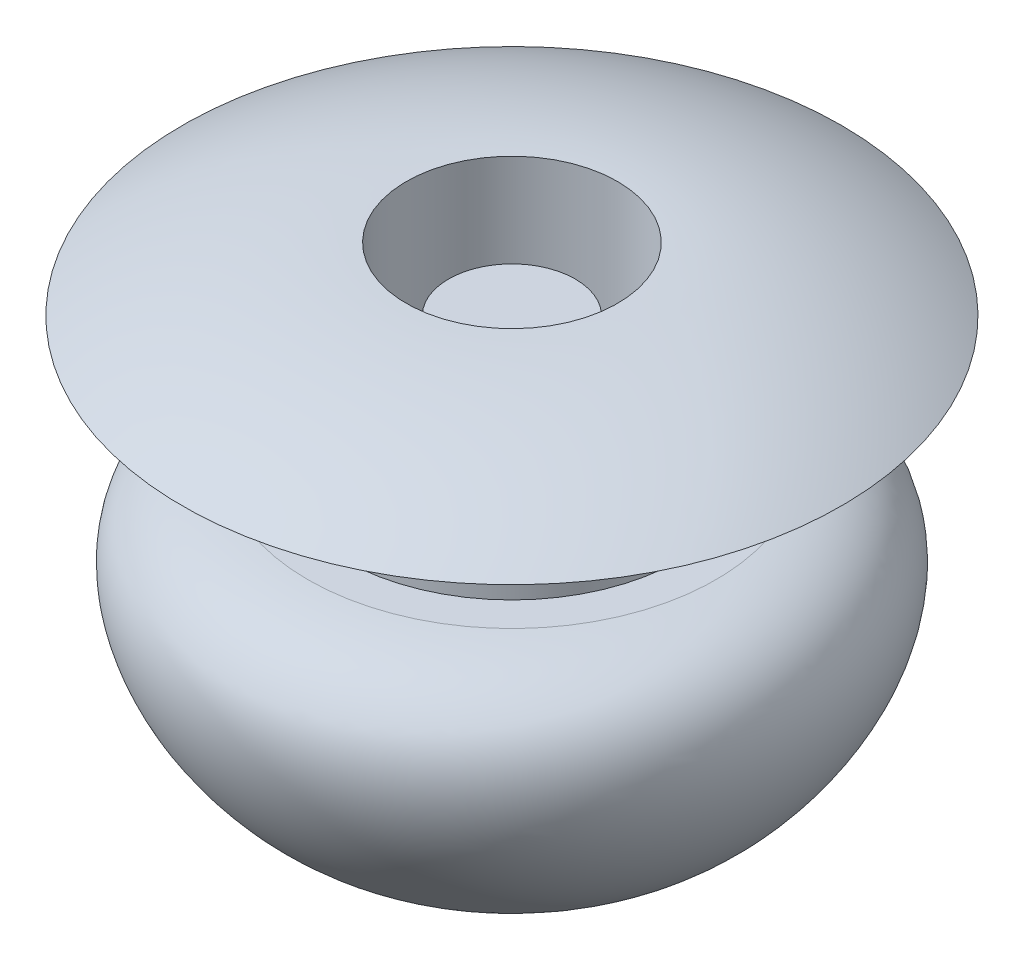
SolidWorks part; units mm, degrees
material "AISI 316 Stal nierdzewna odprężona (SS)"
ref_plane "Płaszczyzna przednia" through (0, 0, 0) normal (0, 0, 1) x (1, 0, 0)
ref_plane "Płaszczyzna górna" through (0, 0, 0) normal (0, 1, 0) x (1, 0, 0)
ref_plane "Płaszczyzna prawa" through (0, 0, 0) normal (1, 0, 0) x (0, 0, -1)
sketch "Szkic1" plane through (0, 0, 0) normal (1, 0, 0) x (0, 0, -1)
  line L1 (0, 0) -> (-0.75, 0)
  line L2 (-0.75, 0) -> (-0.75, -1.7007)
  line L3 (-0.75, -1.7007) -> (-1.25, -1.7007)
  line L4 (-1.25, -1.7007) -> (-1.25, 0.75)
  line L5 (-3.9, 0) -> (-2, 0)
  line L6 (-2, 0) -> (-2, -1.5)
  line L7 (-2, -1.5) -> (-2.4139, -1.5)
  line L8 (0, 0) -> (0, 0.4842) construction
  line L9 (0, -1.7007) -> (0, 0)
  line L10 (0, -1.7007) -> (0, -3.2007)
  line L11 (66.2841, -1.5) -> (70.2841, -1.5) construction
  arc A0 (-1.25, 0.75) -> (-3.9, 0) centre (-1.25, -4.3067) ccw
  ellipse E0 centre (0, -2.4507) end of major axis (-1.75, -2.4507) minor radius 0.75 (-0.956, -3.0789) -> (0, -3.2007) ccw
  spline S0 degree 3 poles (-2.4139, -1.5) (-3.8675, -1.6697) (-3.5289, -3.802) (-1.084, -5.3735) (-0.2718, -3.3749) (-0.956, -3.0789) knots 0 0 0 0 0.464993 0.721928 1 1 1 1
  dimension "D1" = 7.8
  dimension "D2" = 2.5
  dimension "D3" = 4
  dimension "D4" = 0.75
  dimension "D5" = 1.5
  dimension "D6" = 1.5
  dimension "D7" = 3.5
  dimension "D8" = 3.1855
  dimension "D9" = 2.5026
  dimension "D10" = 1.9
  dimension "D11" = 1.5789
  dimension "D12" = 0.5792
  dimension "D13" = 4.8278
  dimension "D14" = 3.3858
  dimension "D15" = 2.8395
  dimension "D16" = 1.25
  dimension "D17" = 0.6409
  dimension "D18" = 0.956
revolve "Obrót1" add sketch "Szkic1" angle 360 about L8
